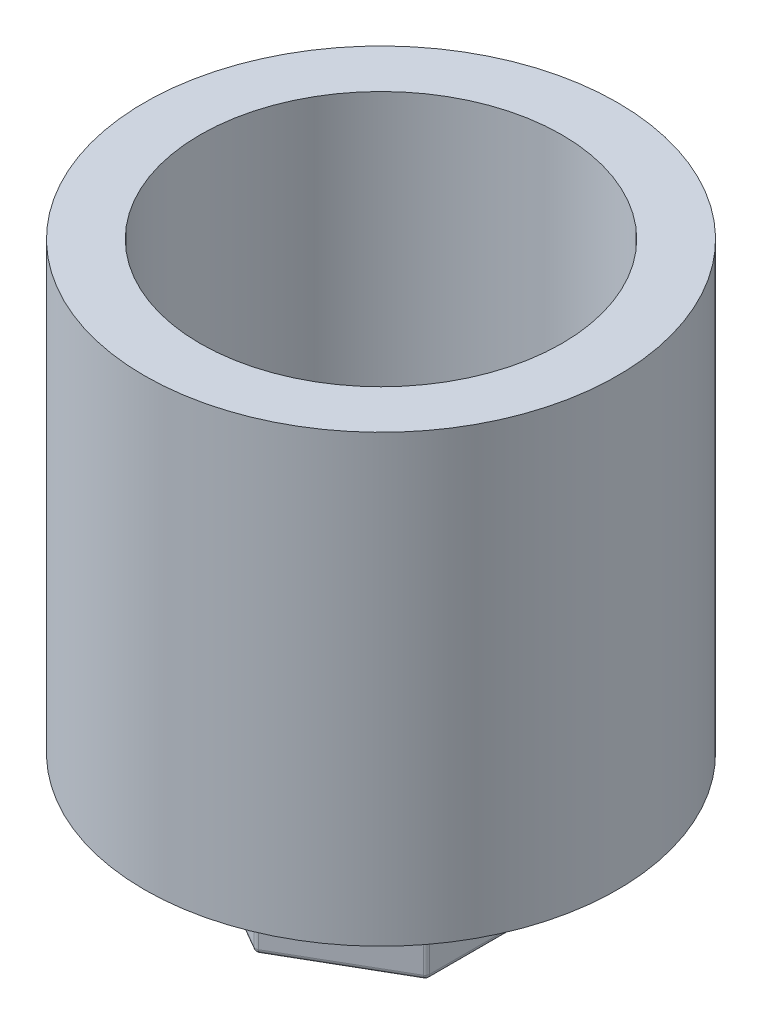
SolidWorks part; units mm, degrees
material "AISI 304"
ref_plane "Front Plane" through (0, 0, 0) normal (0, 0, 1) x (1, 0, 0)
ref_plane "Top Plane" through (0, 0, 0) normal (0, 1, 0) x (1, 0, 0)
ref_plane "Right Plane" through (0, 0, 0) normal (1, 0, 0) x (0, 0, -1)
sketch "Sketch1" plane through (0, 0, 0) normal (0, 1, 0) x (1, 0, 0)
  circle A0 centre (0, 0) radius 13.5
  dimension "D1" = 27
extrude "Boss-Extrude1" add sketch "Sketch1" along normal blind 25.4
hole_wizard "7/8-14 Tapped Hole1" positions "Sketch4" profile "Sketch5" tap size "7/8-14" standard "ANSI Inch"
sketch "Sketch4" plane through (0, 25.4, 0) normal (0, 1, 0) x (1, 0, 0)
  point P0 (0, 0)
sketch "Sketch5" plane through (0, 25.4, 0) normal (1, 0, 0) x (0, 0, 1)
  line L0 (0, 0) -> (0, 25.2501)
  line L1 (0, 25.2501) -> (10.3187, 19.05)
  line L2 (10.3187, 19.05) -> (10.3187, 0)
  line L5 (10.3187, 0) -> (0, 0)
  line L10 (0, 25.2501) -> (-10.3188, 19.05) construction
  line L11 (0, -6.35) -> (0, 107.95) construction
  dimension "Tap Drill Dia." = 20.6375
  dimension "Tap Drill Depth" = 19.05
  dimension "Drill Angle" = 118
cosmetic thread "Hole Thread1" parameters "D1"=44.45, "D2"=22.225
sketch "Sketch6" plane through (0, 0, 0) normal (0, -1, 0) x (1, 0, 0)
  line L1 (6.223, 3.5929) -> (0, 7.1857)
  line L2 (0, 7.1857) -> (-6.223, 3.5929)
  line L3 (-6.223, 3.5929) -> (-6.223, -3.5929)
  line L4 (-6.223, -3.5929) -> (0, -7.1857)
  line L5 (0, -7.1857) -> (6.223, -3.5929)
  line L6 (6.223, -3.5929) -> (6.223, 3.5929)
  circle A0 centre (0, 0) radius 6.223 construction
  dimension "D1" = 12.446
extrude "Boss-Extrude2" add sketch "Sketch6" along normal blind 6.35
fillet "Fillet1" radius 0.254 18 edges at (3.1115, 0, -5.3893) (-6.223, 0, 0) (-6.223, -3.175, -3.5929) (0, -3.175, -7.1857) (-3.1115, 0, -5.3893) (6.223, -3.175, -3.5929) (6.223, 0, 0) (-6.223, -3.175, 3.5929) (-3.1115, 0, 5.3893) (6.223, -3.175, 3.5929) (0, -3.175, 7.1857) (3.1115, 0, 5.3893) (3.1115, -6.35, -5.3893) (-3.1115, -6.35, -5.3893) (-6.223, -6.35, 0) (-3.1115, -6.35, 5.3893) (3.1115, -6.35, 5.3893) (6.223, -6.35, 0)
